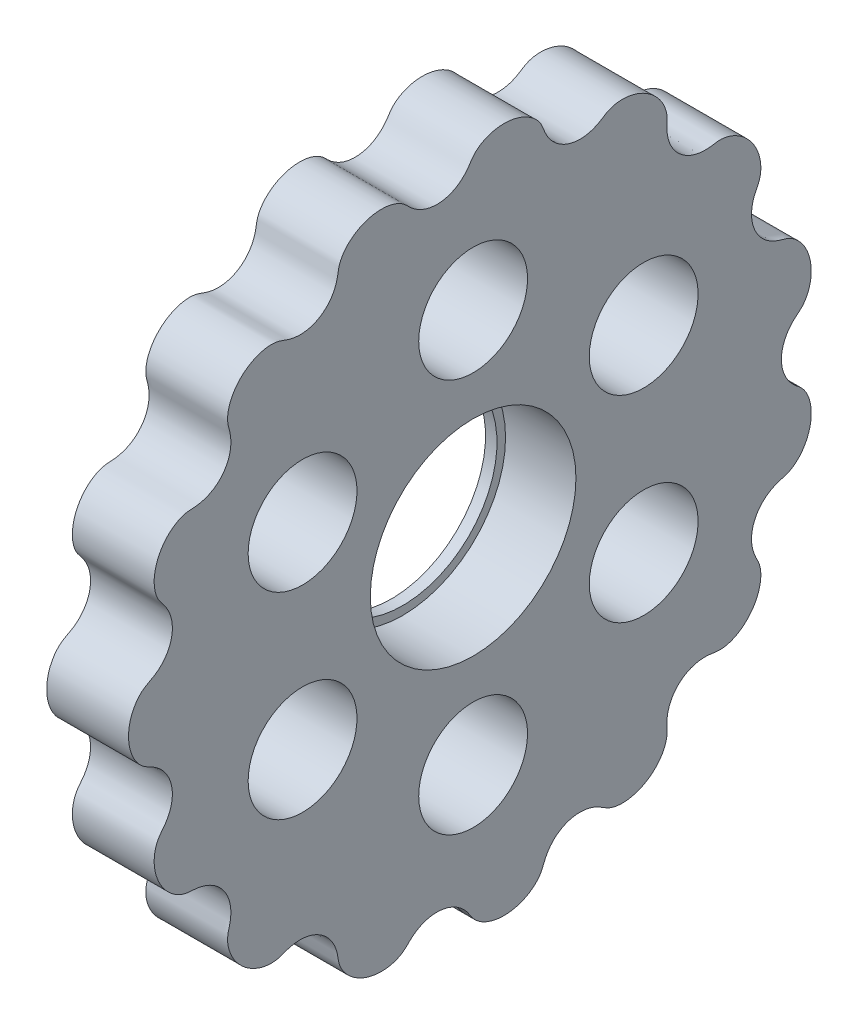
SolidWorks part; units mm, degrees
ref_plane "Front Plane" through (0, 0, 0) normal (0, 0, 1) x (1, 0, 0)
ref_plane "Top Plane" through (0, 0, 0) normal (0, 1, 0) x (1, 0, 0)
ref_plane "Right Plane" through (0, 0, 0) normal (1, 0, 0) x (0, 0, -1)
sketch "Sketch2" plane through (0, 0, 0) normal (0, 0, 1) x (1, 0, 0)
  line L0 (0, 0) -> (58.591, 0) construction
  line L2 (0, 0) -> (18.4, 0)
  line L3 (0, 0) -> (0, 2.5)
  line L4 (0, 2.5) -> (18.4, 2.5)
  line L5 (18.4, 0) -> (18.4, 2.5)
  line L6 (6, 2.5) -> (6, 6)
  line L11 (6, 6) -> (9.97, 6)
  line L16 (12.97, 6) -> (12.97, 3)
  line L17 (12.97, 3) -> (13.6304, 3)
  line L18 (13.6304, 3) -> (13.6304, 2.5)
  line L19 (13.6304, 2.5) -> (6, 2.5)
  line L22 (13.6304, 2.5) -> (16.1104, 2.5)
  line L23 (13.6304, 2.5) -> (13.6304, 4)
  line L24 (13.6304, 4) -> (16.1104, 4)
  line L25 (16.1104, 2.5) -> (16.1104, 4)
  line L27 (6, 6) -> (9.97, 6)
  line L28 (6, 6) -> (6, 9)
  line L29 (6, 9) -> (9.97, 9)
  line L30 (9.97, 6) -> (9.97, 9)
  line L31 (6, 9) -> (6, 8.25)
  line L32 (6, 8.25) -> (5, 8.25)
  line L33 (8.58, 22.001) -> (8.58, 12.476) construction
  line L34 (5, 12.476) -> (12.16, 12.476)
  line L35 (9.97, 9) -> (12.16, 9)
  line L36 (5, 7.5) -> (3, 7.5)
  line L37 (5, 8.25) -> (5, 12.476)
  line L38 (5, 7.5) -> (5, 14)
  line L39 (5, 14) -> (3, 14)
  line L40 (3, 7.5) -> (3, 14)
  line L41 (5, 22.001) -> (12.16, 22.001)
  line L42 (5, 22.001) -> (5, 30.1625)
  line L43 (5, 30.1625) -> (12.16, 30.1625)
  line L44 (12.16, 22.001) -> (12.16, 30.1625)
  line L49 (16.6304, 22.001) -> (16.6304, 7.5)
  line L51 (23.0104, 7.5) -> (23.0104, 6.5)
  line L54 (16.1104, 4) -> (13.6304, 4)
  line L56 (18.0304, 7.5) -> (23.0104, 7.5)
  line L57 (13.16, 22.001) -> (16.6304, 22.001)
  line L58 (16.1104, 3.5) -> (20.0104, 3.5)
  line L59 (29.9004, 14) -> (26.9004, 11)
  line L60 (4, 31.75) -> (18.0304, 31.75)
  line L61 (18.0304, 7.5) -> (23.0104, 7.5)
  line L62 (18.0304, 7.5) -> (18.0304, 12)
  line L63 (18.0304, 12) -> (23.0104, 12)
  line L64 (23.0104, 7.5) -> (23.0104, 12)
  line L65 (18.0304, 31.75) -> (18.0304, 12)
  line L66 (23.0104, 11) -> (26.9004, 11)
  line L67 (34.8004, 23) -> (31.3004, 19.5)
  line L68 (35.8004, 31) -> (38.7904, 33.99)
  line L69 (29.9004, 14) -> (29.9004, 15)
  line L70 (29.9004, 15) -> (22.9304, 15)
  line L71 (22.9304, 15) -> (21.0304, 15)
  line L72 (18.0304, 7.5) -> (16.6304, 7.5)
  line L73 (21.0304, 15) -> (21.0304, 43)
  line L74 (20.0304, 40) -> (10.0704, 40)
  line L75 (10.0704, 40) -> (4, 40)
  line L76 (21.0304, 43) -> (20.0304, 43)
  line L77 (22.9304, 15) -> (29.9004, 15)
  line L78 (22.9304, 15) -> (22.9304, 21)
  line L79 (22.9304, 21) -> (29.9004, 21)
  line L80 (29.9004, 15) -> (29.9004, 21)
  line L81 (10.0704, 40) -> (20.0304, 40)
  line L82 (10.0704, 40) -> (10.0704, 50)
  line L83 (10.0704, 50) -> (20.0304, 50)
  line L84 (20.0304, 40) -> (20.0304, 50)
  line L85 (4, 40) -> (4, 31.75)
  line L86 (12.97, 3) -> (12.97, 2.5)
  line L87 (31.3004, 19.5) -> (29.9004, 19.5)
  line L88 (21.51, 63.5) -> (21.51, 44)
  line L89 (21.51, 63.5) -> (25.9304, 63.5)
  line L90 (25.9304, 63.5) -> (25.9304, 25)
  line L91 (27.8304, 25) -> (25.9304, 25)
  line L92 (10.0704, 48) -> (9, 48)
  line L93 (9, 48) -> (9, 53.476)
  line L94 (9, 53.476) -> (20.0304, 53.476)
  line L95 (20.0304, 53.476) -> (20.0304, 50)
  line L96 (14.5152, 63.001) -> (14.5152, 53.476) construction
  line L97 (9, 63.001) -> (20.0304, 63.001)
  line L98 (9, 63.001) -> (9, 68.2625)
  line L99 (9, 68.2625) -> (20.0304, 68.2625)
  line L100 (20.0304, 63.001) -> (20.0304, 68.2625)
  line L101 (12.97, 6) -> (11.97, 6)
  line L102 (9, 42.5) -> (5, 42.5)
  line L103 (9, 42.5) -> (9, 55)
  line L104 (9, 55) -> (5, 55)
  line L105 (5, 42.5) -> (5, 55)
  line L106 (9.97, 6) -> (10.87, 6)
  line L107 (27.8304, 25) -> (34.8004, 25)
  line L108 (34.8004, 25) -> (34.8004, 23)
  line L109 (0, 0) -> (-2, 0)
  line L110 (0, 0) -> (0, 11)
  line L111 (27.8304, 25) -> (34.8004, 25)
  line L112 (27.8304, 25) -> (27.8304, 32.5)
  line L113 (27.8304, 32.5) -> (34.8004, 32.5)
  line L114 (34.8004, 25) -> (34.8004, 32.5)
  line L115 (35.8004, 31) -> (34.8004, 31)
  line L116 (27.8304, 32.5) -> (27.8304, 64.5)
  line L117 (21.1827, 74.025) -> (6.8477, 74.025)
  line L118 (6.8477, 74.025) -> (6.8477, 76.2)
  line L119 (38.7904, 47.29) -> (30.8304, 55.25)
  line L120 (0, 11) -> (-2, 11)
  line L121 (38.7904, 43.815) -> (30.8529, 43.815)
  line L123 (-4.8, 69.85) -> (1.55, 76.2)
  line L124 (38.7904, 47.29) -> (38.7904, 33.99)
  line L125 (-2, 0) -> (-2, 11)
  line L126 (38.7904, 37.465) -> (30.8529, 37.465)
  line L127 (30.8529, 43.815) -> (30.8529, 37.465)
  line L128 (6, 2.5) -> (6, 0)
  line L129 (0, 63.5) -> (0, 30)
  line L132 (5, 63.5) -> (0, 63.5)
  line L136 (-1.8, 30) -> (-11.76, 30)
  line L138 (-13.76, 25.4) -> (-2, 25.4)
  line L139 (-2, 25.4) -> (-2, 11.5)
  line L140 (27.8304, 64.5) -> (21.1827, 64.5)
  line L141 (-1.8, 30) -> (-11.76, 30)
  line L142 (-1.8, 30) -> (-1.8, 39)
  line L143 (-1.8, 39) -> (-11.76, 39)
  line L144 (-11.76, 30) -> (-11.76, 39)
  line L145 (21.1827, 64.5) -> (21.1827, 74.025)
  line L146 (-12.76, 37) -> (-12.76, 47.29)
  line L147 (-12.76, 37) -> (-11.76, 37)
  line L148 (30.8304, 55.25) -> (30.8304, 76.2)
  line L149 (11.97, 6) -> (11.97, 5.45)
  line L154 (-2, 11.5) -> (1, 11.5)
  line L155 (5, 60.6197) -> (24.05, 60.6197)
  line L160 (5, 60.6197) -> (5, 55.8572)
  line L161 (5, 55.8572) -> (24.05, 55.8572)
  line L166 (24.05, 60.6197) -> (24.05, 55.8572)
  line L167 (5, 60.6197) -> (24.05, 55.8572) construction
  line L172 (5, 55.8572) -> (24.05, 60.6197) construction
  line L173 (24.05, 62.2072) -> (25.9304, 62.2072)
  line L174 (11.97, 5.45) -> (10.87, 5.45)
  line L175 (10.87, 6) -> (10.87, 5.45)
  line L176 (24.05, 62.2072) -> (24.05, 54.2697)
  line L177 (24.05, 54.2697) -> (25.9304, 54.2697)
  line L178 (25.9304, 62.2072) -> (25.9304, 54.2697)
  line L179 (24.05, 62.2072) -> (25.9304, 54.2697) construction
  line L180 (24.05, 54.2697) -> (25.9304, 62.2072) construction
  line L181 (3, 19.6197) -> (15.7, 19.6197)
  line L182 (3, 19.6197) -> (3, 14.8572)
  line L183 (3, 14.8572) -> (15.7, 14.8572)
  line L184 (15.7, 19.6197) -> (15.7, 14.8572)
  line L185 (3, 19.6197) -> (15.7, 14.8572) construction
  line L186 (3, 14.8572) -> (15.7, 19.6197) construction
  line L187 (15.7, 21.2072) -> (16.6304, 21.2072)
  line L188 (15.7, 21.2072) -> (15.7, 13.2697)
  line L189 (15.7, 13.2697) -> (16.6304, 13.2697)
  line L190 (16.6304, 21.2072) -> (16.6304, 13.2697)
  line L191 (15.7, 21.2072) -> (16.6304, 13.2697) construction
  line L192 (15.7, 13.2697) -> (16.6304, 21.2072) construction
  line L193 (1, 11.5) -> (1, 6.5)
  line L194 (1, 6.5) -> (3, 6.5)
  line L195 (23.0104, 6.5) -> (20.0104, 3.5)
  line L196 (5, 63.5) -> (5, 42.5)
  line L197 (5, 42.5) -> (3, 42.5)
  line L198 (3, 42.5) -> (3, 6.5)
  line L199 (6, 0) -> (12.97, 0)
  line L200 (12.97, 0) -> (12.97, 2.5)
  line L201 (18.0304, 31.75) -> (18.0304, 35.875)
  line L202 (18.0304, 35.875) -> (21.0304, 35.875)
  line L203 (30.8304, 76.2) -> (6.8477, 76.2)
  line L204 (3.4027, 69.85) -> (7.8477, 69.85) construction
  line L205 (7.8477, 67.4687) -> (26.8977, 67.4688)
  line L206 (7.8477, 74.025) -> (7.8477, 64.5)
  line L207 (7.8477, 64.5) -> (-1.8, 64.5)
  line L208 (-1.8, 64.5) -> (-1.8, 39)
  line L209 (-12.76, 47.29) -> (-4.8, 55.25)
  line L210 (-4.8, 55.25) -> (-4.8, 69.85)
  line L211 (7.8477, 67.4687) -> (7.8477, 72.2313)
  line L212 (7.8477, 72.2313) -> (26.8977, 72.2313)
  line L213 (26.8977, 67.4688) -> (26.8977, 72.2313)
  line L214 (26.8977, 73.8187) -> (30.8304, 73.8187)
  line L215 (26.8977, 73.8187) -> (26.8977, 65.8813)
  line L216 (26.8977, 65.8813) -> (30.8304, 65.8813)
  line L217 (30.8304, 73.8187) -> (30.8304, 65.8813)
  line L218 (3.4027, 72.2313) -> (25.6277, 72.2313)
  line L219 (3.4027, 72.2313) -> (3.4027, 67.4687)
  line L220 (3.4027, 67.4687) -> (25.6277, 67.4687)
  line L221 (25.6277, 72.2313) -> (25.6277, 67.4687)
  line L222 (25.6277, 69.85) -> (21.1827, 69.85) construction
  line L223 (21.51, 44) -> (22.9304, 44)
  line L224 (22.9304, 44) -> (22.9304, 21)
  line L225 (13.6304, 4) -> (13.6304, 12.2697)
  line L226 (13.6304, 12.2697) -> (13.16, 12.2697)
  line L227 (13.16, 12.2697) -> (13.16, 22.001)
  line L228 (12.16, 9) -> (12.16, 12.476)
  line L229 (-1.8, 30) -> (0, 30)
  line L230 (9, 65.6317) -> (3.4027, 65.6317) construction
  line L231 (20.0304, 65.6317) -> (25.6277, 65.6317) construction
  line L232 (1.55, 76.2) -> (6.8477, 76.2)
  line L233 (-11.76, 30) -> (-13.76, 30)
  line L234 (-13.76, 30) -> (-13.76, 25.4)
  circle A0 centre (26.8804, 25.95) radius 0.95
  circle A1 centre (21.9804, 15.95) radius 0.95
  circle A2 centre (17.3304, 8.2) radius 0.7
  circle A3 centre (10.42, 6.45) radius 0.45
  circle A4 centre (-0.9, 30.9) radius 0.9
  point P7 (24.9902, 58.2385)
  point P131 (16.1652, 17.2385)
  point P135 (14.525, 58.2385)
  point P146 (9.35, 17.2385)
sketch "Sketch3" plane through (0, 0, 0) normal (1, 0, 0) x (0, 0, -1)
  line L0 (0, 0) -> (0, 69.85) construction
  line L1 (0, 0) -> (13.6271, 68.5079) construction
  line L2 (0, 0) -> (0, 58.2385) construction
  line L3 (0, 0) -> (50.436, 29.1192) construction
  line L4 (0, 0) -> (0, 31.75) construction
  line L5 (0, 0) -> (12.1502, 29.3332) construction
  line L6 (0, 0) -> (0, 17.2385) construction
  line L7 (0, 0) -> (14.929, 8.6192) construction
  line L8 (0, 0) -> (0, 58.2385) construction
  line L9 (0, 0) -> (50.436, 29.1192) construction
  line L10 (0, 0) -> (5.9583, 29.9542) construction
  line L11 (0, 0) -> (16.9677, 25.394) construction
  circle A0 centre (0, 0) radius 69.85 construction
  circle A1 centre (0, 0) radius 58.2385 construction
  circle A2 centre (0, 0) radius 31.75 construction
  circle A3 centre (0, 0) radius 17.2385 construction
  circle A4 centre (0, 69.85) radius 3.175
  circle A5 centre (0, 58.2385) radius 4.7625
  circle A6 centre (0, 31.75) radius 3.175
  circle A7 centre (0, 17.2385) radius 4.7625
  circle A8 centre (13.6271, 68.5079) radius 3.175
  circle A9 centre (26.7304, 64.533) radius 3.175
  circle A10 centre (38.8066, 58.0782) radius 3.175
  circle A11 centre (49.3914, 49.3914) radius 3.175
  circle A12 centre (58.0782, 38.8066) radius 3.175
  circle A13 centre (64.533, 26.7304) radius 3.175
  circle A14 centre (68.5079, 13.6271) radius 3.175
  circle A15 centre (69.85, 0) radius 3.175
  circle A16 centre (68.5079, -13.6271) radius 3.175
  circle A17 centre (64.533, -26.7304) radius 3.175
  circle A18 centre (58.0782, -38.8066) radius 3.175
  circle A19 centre (49.3914, -49.3914) radius 3.175
  circle A20 centre (38.8066, -58.0782) radius 3.175
  circle A21 centre (26.7304, -64.533) radius 3.175
  circle A22 centre (13.6271, -68.5079) radius 3.175
  circle A23 centre (0, -69.85) radius 3.175
  circle A24 centre (-13.6271, -68.5079) radius 3.175
  circle A25 centre (-26.7304, -64.533) radius 3.175
  circle A26 centre (-38.8066, -58.0782) radius 3.175
  circle A27 centre (-49.3914, -49.3914) radius 3.175
  circle A28 centre (-58.0782, -38.8066) radius 3.175
  circle A29 centre (-64.533, -26.7304) radius 3.175
  circle A30 centre (-68.5079, -13.6271) radius 3.175
  circle A31 centre (-69.85, 0) radius 3.175
  circle A32 centre (-68.5079, 13.6271) radius 3.175
  circle A33 centre (-64.533, 26.7304) radius 3.175
  circle A34 centre (-58.0782, 38.8066) radius 3.175
  circle A35 centre (-49.3914, 49.3914) radius 3.175
  circle A36 centre (-38.8066, 58.0782) radius 3.175
  circle A37 centre (-26.7304, 64.533) radius 3.175
  circle A38 centre (-13.6271, 68.5079) radius 3.175
  circle A47 centre (50.436, 29.1192) radius 4.7625
  circle A48 centre (50.436, -29.1192) radius 4.7625
  circle A49 centre (0, -58.2385) radius 4.7625
  circle A50 centre (-50.436, -29.1192) radius 4.7625
  circle A51 centre (-50.436, 29.1192) radius 4.7625
  circle A58 centre (12.1502, 29.3332) radius 3.175
  circle A59 centre (22.4506, 22.4506) radius 3.175
  circle A60 centre (29.3332, 12.1502) radius 3.175
  circle A61 centre (31.75, 0) radius 3.175
  circle A62 centre (29.3332, -12.1502) radius 3.175
  circle A63 centre (22.4506, -22.4506) radius 3.175
  circle A64 centre (12.1502, -29.3332) radius 3.175
  circle A65 centre (0, -31.75) radius 3.175
  circle A66 centre (-12.1502, -29.3332) radius 3.175
  circle A67 centre (-22.4506, -22.4506) radius 3.175
  circle A68 centre (-29.3332, -12.1502) radius 3.175
  circle A69 centre (-31.75, 0) radius 3.175
  circle A70 centre (-29.3332, 12.1502) radius 3.175
  circle A71 centre (-22.4506, 22.4506) radius 3.175
  circle A72 centre (14.929, 8.6192) radius 4.7625
  circle A73 centre (14.929, -8.6192) radius 4.7625
  circle A74 centre (0, -17.2385) radius 4.7625
  circle A75 centre (-14.929, -8.6192) radius 4.7625
  circle A76 centre (-14.929, 8.6192) radius 4.7625
  circle A77 centre (0, 0) radius 50
  circle A78 centre (0, 0) radius 9
  circle A79 centre (-12.1502, 29.3332) radius 3.175
  circle A80 centre (0, 0) radius 76.2
  circle A81 centre (0, 0) radius 74.025
  circle A82 centre (0, 69.85) radius 3.9687
  circle A83 centre (49.3914, 49.3914) radius 3.9687
  circle A84 centre (69.85, 0) radius 3.9688
  circle A85 centre (49.3914, -49.3914) radius 3.9687
  circle A86 centre (0, -69.85) radius 3.9687
  circle A87 centre (-49.3914, -49.3914) radius 3.9687
  circle A88 centre (-69.85, 0) radius 3.9688
  circle A89 centre (-49.3914, 49.3914) radius 3.9687
  circle A90 centre (0, 69.85) radius 2.3812
  circle A91 centre (13.6271, 68.5079) radius 2.3812
  circle A92 centre (26.7304, 64.533) radius 2.3813
  circle A93 centre (38.8066, 58.0782) radius 2.3812
  circle A94 centre (49.3914, 49.3914) radius 2.3812
  circle A95 centre (58.0782, 38.8066) radius 2.3812
  circle A96 centre (64.533, 26.7304) radius 2.3813
  circle A97 centre (68.5079, 13.6271) radius 2.3813
  circle A98 centre (69.85, 0) radius 2.3813
  circle A99 centre (68.5079, -13.6271) radius 2.3813
  circle A100 centre (64.533, -26.7304) radius 2.3813
  circle A101 centre (58.0782, -38.8066) radius 2.3812
  circle A102 centre (49.3914, -49.3914) radius 2.3812
  circle A103 centre (38.8066, -58.0782) radius 2.3812
  circle A104 centre (26.7304, -64.533) radius 2.3813
  circle A105 centre (13.6271, -68.5079) radius 2.3812
  circle A106 centre (0, -69.85) radius 2.3812
  circle A107 centre (-13.6271, -68.5079) radius 2.3812
  circle A108 centre (-26.7304, -64.533) radius 2.3813
  circle A109 centre (-38.8066, -58.0782) radius 2.3812
  circle A110 centre (-49.3914, -49.3914) radius 2.3812
  circle A111 centre (-58.0782, -38.8066) radius 2.3812
  circle A112 centre (-64.533, -26.7304) radius 2.3812
  arc A113 (3.0399, 30.8338) -> (8.9911, 29.65) centre (5.9583, 29.9542) cw
  arc A114 (14.6081, 27.3234) -> (19.6532, 23.9523) centre (16.9677, 25.394) cw
  arc A115 (23.9523, 19.6532) -> (27.3234, 14.6081) centre (25.394, 16.9677) cw
  arc A116 (29.65, 8.9911) -> (30.8338, 3.0399) centre (29.9542, 5.9583) cw
  arc A117 (30.8338, -3.0399) -> (29.65, -8.9911) centre (29.9542, -5.9583) cw
  arc A118 (27.3234, -14.6081) -> (23.9523, -19.6532) centre (25.394, -16.9677) cw
  arc A119 (19.6532, -23.9523) -> (14.6081, -27.3234) centre (16.9677, -25.394) cw
  arc A120 (8.9911, -29.65) -> (3.0399, -30.8338) centre (5.9583, -29.9542) cw
  arc A121 (-3.0399, -30.8338) -> (-8.9911, -29.65) centre (-5.9583, -29.9542) cw
  arc A122 (-14.6081, -27.3234) -> (-19.6532, -23.9523) centre (-16.9677, -25.394) cw
  arc A123 (-23.9523, -19.6532) -> (-27.3234, -14.6081) centre (-25.394, -16.9677) cw
  arc A124 (-29.65, -8.9911) -> (-30.8338, -3.0399) centre (-29.9542, -5.9583) cw
  arc A125 (-30.8338, 3.0399) -> (-29.65, 8.9911) centre (-29.9542, 5.9583) cw
  arc A126 (-27.3234, 14.6081) -> (-23.9523, 19.6532) centre (-25.394, 16.9677) cw
  arc A127 (-19.6532, 23.9523) -> (-14.6081, 27.3234) centre (-16.9677, 25.394) cw
  arc A128 (-8.9911, 29.65) -> (-3.0399, 30.8338) centre (-5.9583, 29.9542) cw
  arc A129 (26.9875, 0) -> (26.9932, 0.1932) centre (30.2705, 0) cw
  arc A130 (65.0988, 0.2771) -> (65.0875, 0) centre (68.4964, 0) ccw
  circle A131 centre (1.5875, 0) radius 40
  circle A132 centre (1.5875, 0) radius 2.5
  circle A133 centre (1.5875, 0) radius 3
  circle A134 centre (1.5875, 0) radius 43
  circle A135 centre (-68.5079, -13.6271) radius 2.3813
  circle A136 centre (-69.85, 0) radius 2.3813
  circle A137 centre (-68.5079, 13.6271) radius 2.3813
  circle A138 centre (-64.533, 26.7304) radius 2.3812
  circle A139 centre (-58.0782, 38.8066) radius 2.3812
  circle A140 centre (-49.3914, 49.3914) radius 2.3812
  circle A141 centre (-38.8066, 58.0782) radius 2.3812
  circle A142 centre (-26.7304, 64.533) radius 2.3813
  circle A143 centre (-13.6271, 68.5079) radius 2.3812
  circle A144 centre (0, 58.2385) radius 2.3812
  circle A145 centre (0, 58.2385) radius 3.9688
  circle A146 centre (50.436, 29.1192) radius 3.9688
  circle A147 centre (50.436, 29.1192) radius 2.3813
  circle A148 centre (50.436, -29.1192) radius 3.9687
  circle A149 centre (50.436, -29.1192) radius 2.3812
  circle A150 centre (0, -58.2385) radius 3.9687
  circle A151 centre (0, -58.2385) radius 2.3812
  circle A152 centre (-50.436, -29.1192) radius 3.9687
  circle A153 centre (-50.436, -29.1192) radius 2.3812
  circle A154 centre (-50.436, 29.1192) radius 3.9687
  circle A155 centre (-50.436, 29.1192) radius 2.3812
  spline S1 degree 4 number of poles 499 (26.9875, 0) -> (26.9932, 0.1932)
  spline S3 degree 4 number of poles 617 (65.0875, 0) -> (65.0988, 0.2771)
  point P116 (0, 0)
  point P225 (0, 0)
sketch "Sketch4" plane through (0, 0, 0) normal (0, 0, 1) x (1, 0, 0)
  line L0 (6, 9) -> (9.97, 9) construction
  line L1 (9.97, 9) -> (12.16, 9) construction
  line L2 (12.16, 9) -> (12.16, 12.476) construction
  line L3 (6, 9) -> (9.97, 9)
  line L4 (6, 6) -> (6, 9) construction
  line L7 (5, 12.476) -> (12.16, 12.476) construction
  line L8 (5, 8.25) -> (5, 12.476) construction
  line L9 (6, 8.25) -> (5, 8.25) construction
  line L14 (6, 8.25) -> (6, 9)
  line L17 (5, 12.476) -> (12.16, 12.476)
  line L18 (5, 8.25) -> (5, 12.476)
  line L19 (6, 8.25) -> (5, 8.25)
  line L20 (9.97, 9) -> (12.16, 9)
  line L21 (12.16, 9) -> (12.16, 12.476)
revolve "Revolve1" add sketch "Sketch4" angle 360 about L0
sketch "Sketch6" plane through (0, 0, 0) normal (1, 0, 0) x (0, 0, -1)
  circle A0 centre (-14.929, -8.6192) radius 4.7625 construction
  circle A1 centre (0, -17.2385) radius 4.7625 construction
  circle A2 centre (14.929, -8.6192) radius 4.7625 construction
  circle A3 centre (14.929, 8.6192) radius 4.7625 construction
  circle A4 centre (0, 17.2385) radius 4.7625 construction
  circle A5 centre (-14.929, 8.6192) radius 4.7625 construction
  circle A6 centre (-14.929, -8.6192) radius 4.7625
  circle A7 centre (0, -17.2385) radius 4.7625
  circle A8 centre (14.929, -8.6192) radius 4.7625
  circle A9 centre (14.929, 8.6192) radius 4.7625
  circle A10 centre (0, 17.2385) radius 4.7625
  circle A11 centre (-14.929, 8.6192) radius 4.7625
  circle A12 centre (0, 0) radius 9 construction
  circle A13 centre (0, 0) radius 9
  arc A14 (26.9932, 0.1932) -> (26.9875, 0) centre (30.2705, 0) ccw construction
  arc A15 (26.9932, 0.1932) -> (26.9875, 0) centre (30.2705, 0) ccw
  spline S0 degree 4 number of poles 499 (26.9875, 0) -> (26.9932, 0.1932) construction
  spline S1 degree 4 number of poles 499 (26.9875, 0) -> (26.9932, 0.1932)
extrude "Boss-Extrude1" add sketch "Sketch6" along normal up to vertex (12.16 mm away) from vertex contours S1 A15 A13 A11 A10 A9 A8 A7 A6 region at (0, 0.1216, -26.1422) up to point (12.16, 12.476, 0) starting at point (5, 12.476, 0)
